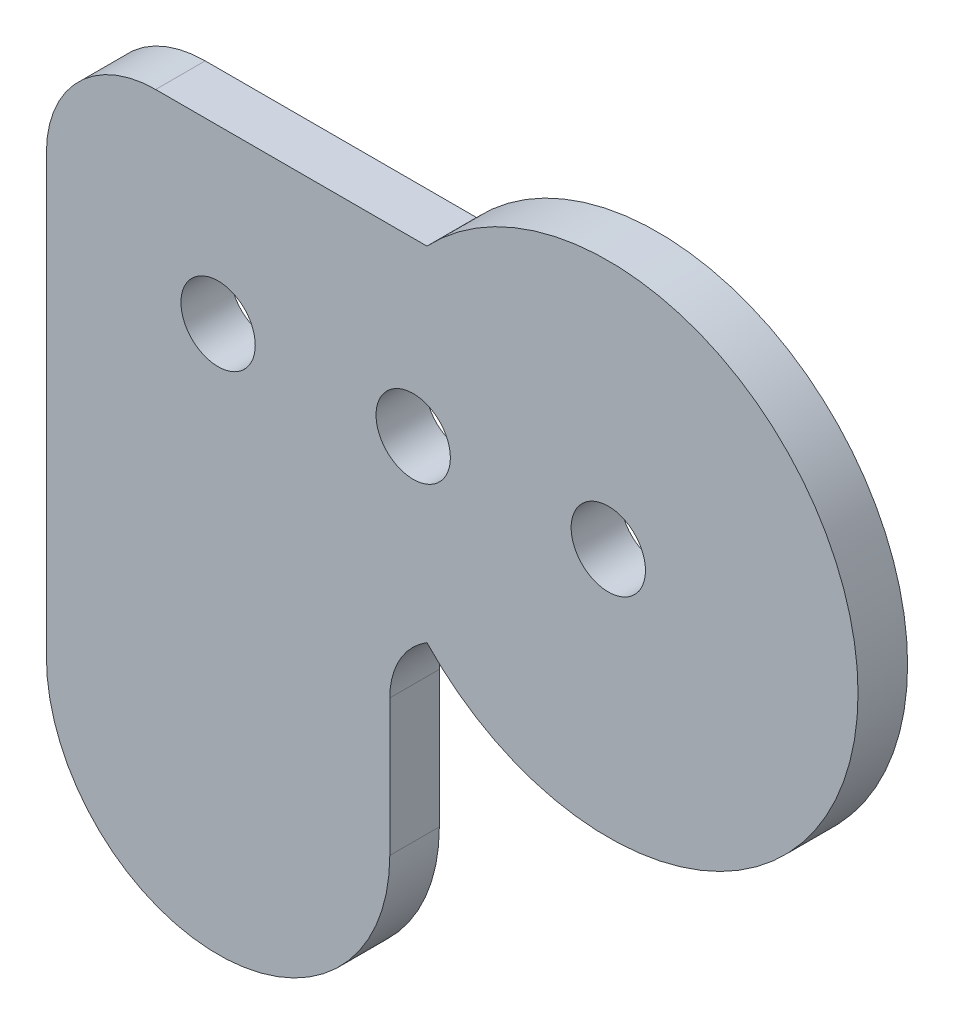
SolidWorks part; units mm, degrees
ref_plane "Front Plane" through (0, 0, 0) normal (0, 0, 1) x (1, 0, 0)
ref_plane "Top Plane" through (0, 0, 0) normal (0, 1, 0) x (1, 0, 0)
ref_plane "Right Plane" through (0, 0, 0) normal (1, 0, 0) x (0, 0, -1)
sketch "Sketch1" plane through (0, 0, 0) normal (0, 0, 1) x (1, 0, 0)
  line L0 (-11.619, 11) -> (-36, 11)
  line L1 (-36, 11) -> (-36, -24)
  line L2 (-14, -24) -> (-14, -11)
  line L3 (-14, -11) -> (-11.619, -11)
  arc A0 (-11.619, -11) -> (-11.619, 11) centre (0, 0) ccw
  arc A1 (-36, -24) -> (-14, -24) centre (-25, -24) ccw
  dimension "D1" = 32
  dimension "D7" = 25
  dimension "D2" = 11
  dimension "D3" = 11
  dimension "D4" = 24
  dimension "D6" = 22
extrude "Boss-Extrude1" add sketch "Sketch1" along normal blind 3.175
fillet "Fillet1" radius 7 1 edges at (-36, 11, 1.5875)
fillet "Fillet2" radius 5 1 edges at (-14, -11, 1.5875)
sketch "Sketch2" plane through (0, 0, 3.175) normal (0, 0, 1) x (1, 0, 0)
  circle A0 centre (0, 0) radius 2.3813
  dimension "D1" = 4.7625
extrude "Cut-Extrude1" cut sketch "Sketch2" against normal through all
pattern_linear "LPattern1" count 3 spacing 12.5 along (-1, 0, 0) of "Cut-Extrude1"
